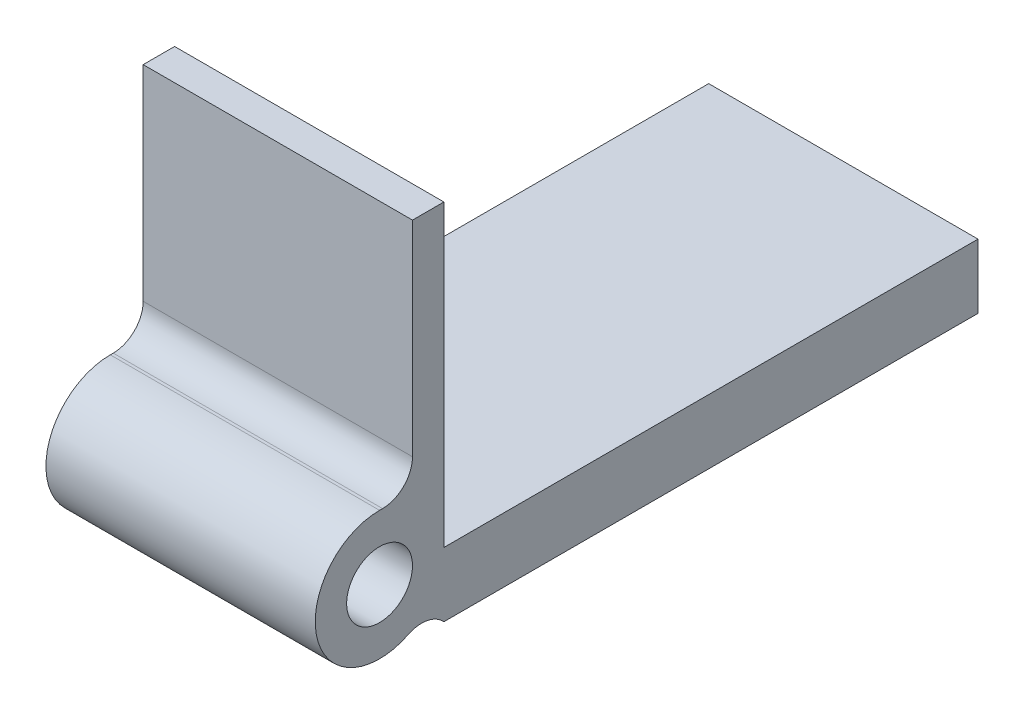
SolidWorks part; units mm, degrees
ref_plane "Front Plane" through (0, 0, 0) normal (0, 0, 1) x (1, 0, 0)
ref_plane "Top Plane" through (0, 0, 0) normal (0, 1, 0) x (1, 0, 0)
ref_plane "Right Plane" through (0, 0, 0) normal (1, 0, 0) x (0, 0, -1)
sketch "Sketch1" plane through (0, 0, 0) normal (1, 0, 0) x (0, 0, -1)
  line L0 (0, 2.15) -> (1.1, 2.15)
  line L1 (2.15, -2.15) -> (20, -2.15)
  line L3 (2.15, 0) -> (20, 0)
  line L4 (20, -2.15) -> (20, 0)
  line L7 (2.15, 0) -> (2.15, 10)
  line L8 (2.15, 10) -> (1.1, 10)
  line L9 (1.1, 2.15) -> (1.1, 10)
  line L10 (1.5203, -1.5203) -> (2.15, -2.15)
  circle A1 centre (0, 0) radius 1.1
  arc A3 (0, 2.15) -> (1.5203, -1.5203) centre (0, 0) ccw
extrude "Boss-Extrude1" add sketch "Sketch1" along normal mid plane 9
fillet "Fillet1" radius 1 2 edges at (0, 2.15, -1.1) (0, -1.5203, -1.5203)
